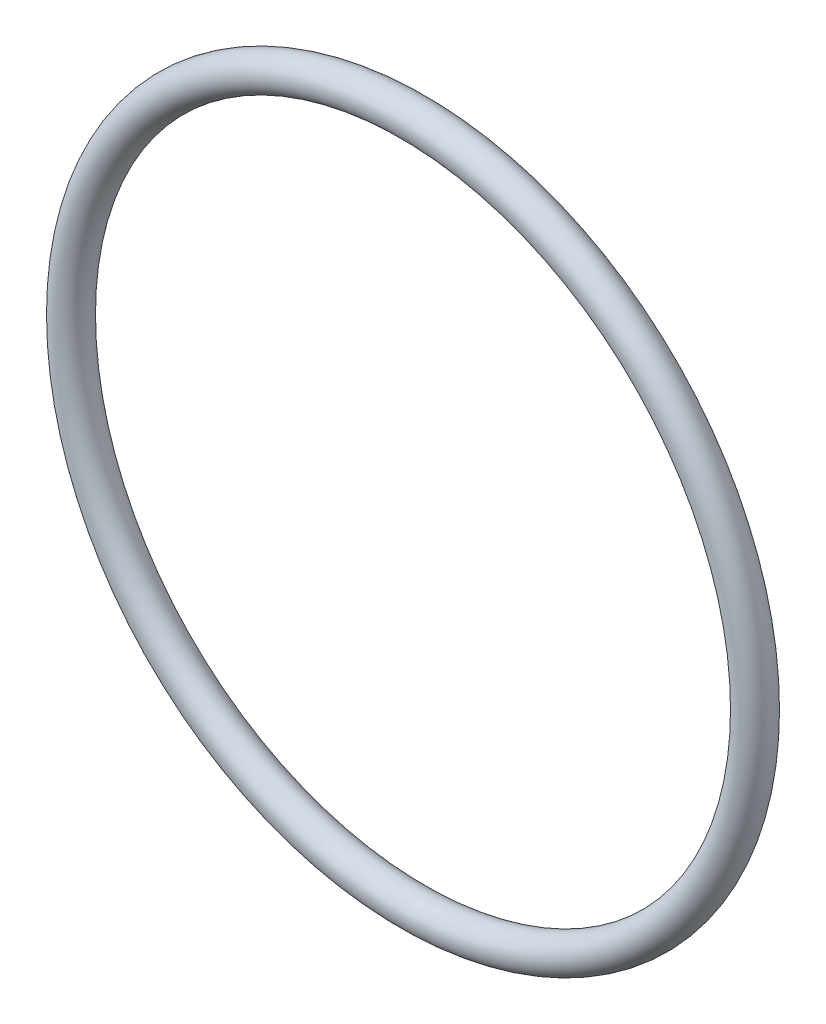
SolidWorks part; units mm, degrees
ref_plane "Front Plane" through (0, 0, 0) normal (0, 0, 1) x (1, 0, 0)
ref_plane "Top Plane" through (0, 0, 0) normal (0, 1, 0) x (1, 0, 0)
ref_plane "Right Plane" through (0, 0, 0) normal (1, 0, 0) x (0, 0, -1)
ref_axis "CL" through (0, 0, 55) along (0, 0, -1)
sketch "Sketch1" plane through (0, 0, 0) normal (0, 0, 1) x (1, 0, 0)
  line L0 (-20, 0) -> (20, 0) construction
  circle A0 centre (0, 0) radius 15.55
  circle A1 centre (0, 0) radius 14.05
  point P4 (14.05, 0)
  point P5 (15.55, 0)
  point P8 (0, 0)
  point P9 (0, 15.55)
  point P10 (0, -15.55)
  dimension "D1" = 31.1
  dimension "ID" = 28.1
  dimension "Width" = 1.5
sketch "Sketch2" plane through (0, 0, 0) normal (0, 1, 0) x (1, 0, 0)
  line L0 (-15.55, 0) -> (15.55, 0) construction
  line L1 (0, 0.75) -> (0, -0.75) construction
  circle A0 centre (14.8, 0) radius 0.75
  point P8 (0, 0)
  point P11 (14.8, 0.75)
revolve "Revolve1" add sketch "Sketch2" angle 360 about L1
sketch "Sketch3" plane through (0, 0, 0) normal (1, 0, 0) x (0, 0, -1)
  line L0 (-0.75, 0) -> (0.75, 0) construction
  line L1 (0.75, -14.8) -> (0.75, 14.8) construction
  line L3 (-0.75, 15.55) -> (0.75, 15.55) construction
  line L4 (-0.75, 15.55) -> (-0.75, -15.55) construction
  line L5 (-0.75, -15.55) -> (0.75, -15.55) construction
  line L6 (0.75, 15.55) -> (0.75, -15.55) construction
  point P2 (0, 0)
